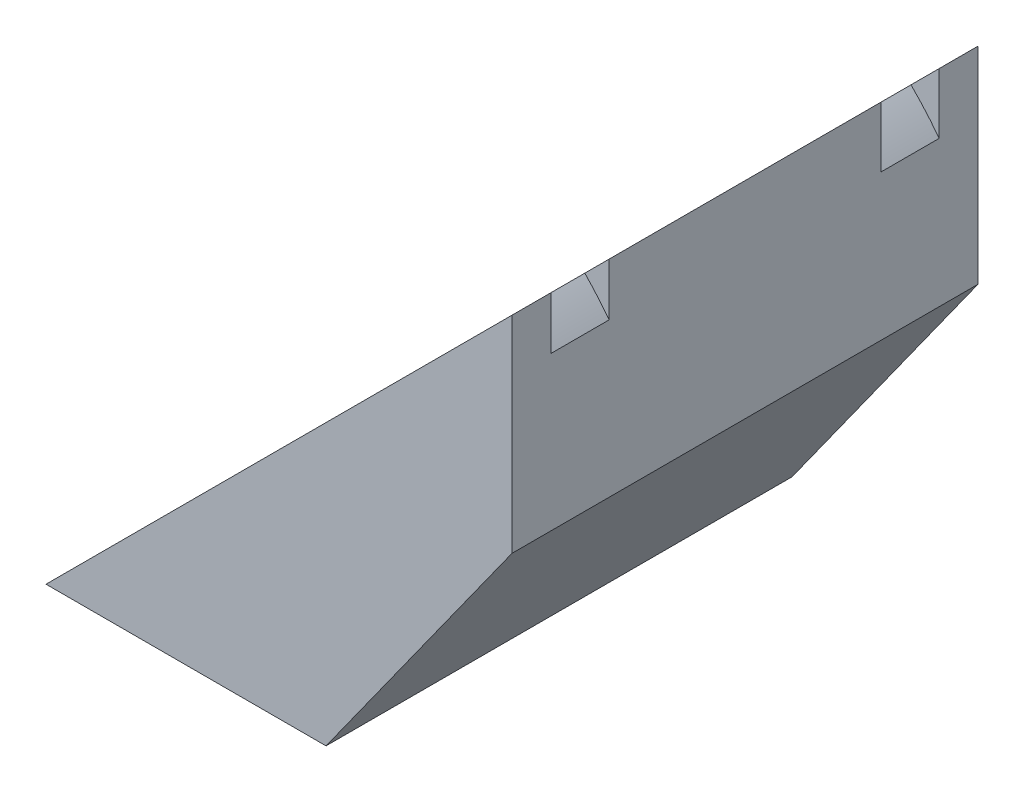
SolidWorks part; units mm, degrees
ref_plane "Спереди" through (0, 0, 0) normal (0, 0, 1) x (1, 0, 0)
ref_plane "Сверху" through (0, 0, 0) normal (0, 1, 0) x (1, 0, 0)
ref_plane "Справа" through (0, 0, 0) normal (1, 0, 0) x (0, 0, -1)
sketch "Эскиз1" plane through (0, 0, 0) normal (0, 1, 0) x (1, 0, 0)
  line L1 (-12, 12) -> (12, 12)
  line L2 (-12, 12) -> (-12, -12)
  line L3 (-12, -12) -> (12, -12)
  line L4 (12, 12) -> (12, -12)
  line L5 (-12, 12) -> (12, -12) construction
  line L6 (-12, -12) -> (12, 12) construction
  point P0 (0, 0)
  dimension "D1" = 24
  dimension "D2" = 24
extrude "Бобышка-Вытянуть1" add sketch "Эскиз1" along normal blind 24
ref_plane "Плоскость1" through (0, 12, 0) normal (0, 1, 0) x (1, 0, 0)
ref_axis "Ось1" through (0, 12, 50) along (0, 0, -1)
ref_plane "Плоскость2" through (-6, 6, 0) normal (-0.7071, 0.7071, 0) x (0.7071, 0.7071, 0)
sketch "Эскиз2" plane through (-6, 6, 0) normal (-0.7071, 0.7071, 0) x (0.7071, 0.7071, 0)
  line L1 (-35.866, 32.1628) -> (35.866, 32.1628)
  line L2 (-35.866, 32.1628) -> (-35.866, -32.1628)
  line L3 (-35.866, -32.1628) -> (35.866, -32.1628)
  line L4 (35.866, 32.1628) -> (35.866, -32.1628)
  line L5 (-35.866, 32.1628) -> (35.866, -32.1628) construction
  line L6 (-35.866, -32.1628) -> (35.866, 32.1628) construction
  point P0 (0, 0)
extrude "Вырез-Вытянуть1" cut sketch "Эскиз2" along normal blind 24
ref_axis "Ось2" through (12, 24, 12) along (-0.5774, -0.5774, -0.5774)
ref_axis "Ось3" through (12, 24, -12) along (-0.5774, -0.5774, 0.5774)
ref_point "Точка1"
sketch "Эскиз3" plane through (-6, 6, 0) normal (-0.7071, 0.7071, 0) x (0.7071, 0.7071, 0)
  line L1 (18.0353, 9.55) -> (-1.0647, 9.55)
  line L2 (18.0353, 9.55) -> (18.0353, -9.55)
  line L3 (18.0353, -9.55) -> (-1.0647, -9.55)
  line L4 (-1.0647, 9.55) -> (-1.0647, -9.55)
  line L5 (18.0353, 9.55) -> (-1.0647, -9.55) construction
  line L6 (18.0353, -9.55) -> (-1.0647, 9.55) construction
  point P0 (8.4853, 0)
  dimension "D1" = 19.1
  dimension "D2" = 19.1
extrude "Вырез-Вытянуть2" cut sketch "Эскиз3" against normal blind 0.75
ref_plane "Плоскость3" through (0, 0, 10) normal (0, 0, 1) x (1, 0, 0)
sketch "Эскиз4" plane through (0, 0, 10) normal (0, 0, 1) x (1, 0, 0)
  circle A0 centre (0, 12.2889) radius 15
  circle A1 centre (0, 12.2889) radius 20.3162
  dimension "D1" = 30
extrude "Вырез-Вытянуть3" cut sketch "Эскиз4" against normal blind 3
ref_plane "Плоскость4" through (0, 0, -10) normal (0, 0, 1) x (1, 0, 0)
sketch "Эскиз5" plane through (0, 0, -10) normal (0, 0, 1) x (1, 0, 0)
  circle A0 centre (0, 11.885) radius 15
  circle A1 centre (0, 11.885) radius 19.7788
  dimension "D1" = 30
extrude "Вырез-Вытянуть4" cut sketch "Эскиз5" along normal blind 3
sketch "Эскиз6" plane through (0, 0, 0) normal (0, 1, 0) x (1, 0, 0)
  circle A0 centre (0, 0) radius 1.2
  dimension "D1" = 2.4
extrude "Вырез-Вытянуть5" cut sketch "Эскиз6" along normal blind 8
sketch "Эскиз7" plane through (0, 0, 0) normal (1, 0, 0) x (0, 0, -1)
  line L1 (4.0368, -8) -> (-4.0368, -8)
  line L2 (4.0368, -8) -> (4.0368, 8)
  line L3 (4.0368, 8) -> (-4.0368, 8)
  line L4 (-4.0368, -8) -> (-4.0368, 8)
  line L5 (4.0368, -8) -> (-4.0368, 8) construction
  line L6 (4.0368, 8) -> (-4.0368, -8) construction
  point P0 (0, 0)
  dimension "D1" = 16
extrude "Вырез-Вытянуть6" cut sketch "Эскиз7" against normal blind 0.1 and the other way blind 0.1
sketch "Эскиз8" plane through (0, 0, 0) normal (0, 0, 1) x (1, 0, 0)
  line L0 (0.9261, -2.0903) -> (18.081, 21.871)
  line L1 (18.081, 21.871) -> (23.5446, -7.4697)
  line L2 (23.5446, -7.4697) -> (0.9261, -2.0903)
extrude "Вырез-Вытянуть7" cut sketch "Эскиз8" against normal blind 15 and the other way blind 15
